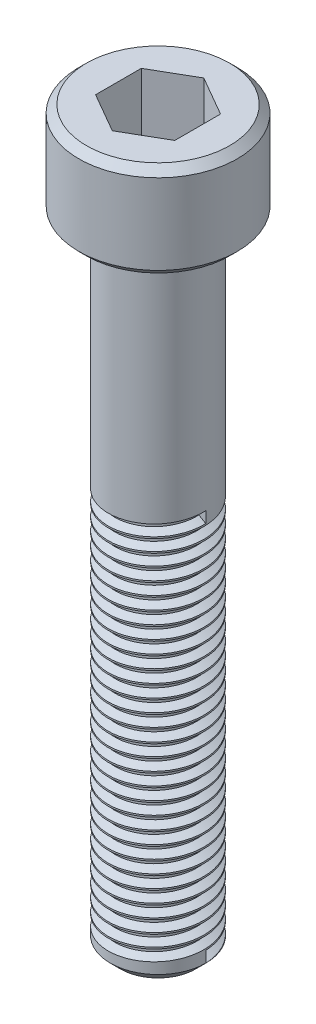
SolidWorks part; units mm, degrees
ref_plane "Front Plane" through (0, 0, 0) normal (0, 0, 1) x (1, 0, 0)
ref_plane "Top Plane" through (0, 0, 0) normal (0, 1, 0) x (1, 0, 0)
ref_plane "Right Plane" through (0, 0, 0) normal (1, 0, 0) x (0, 0, -1)
sketch "Sketch1" plane through (0, 0, 0) normal (0, 0, 1) x (1, 0, 0)
  line L0 (0, 0) -> (0, 43.3309) construction
  line L1 (0, 0) -> (-2.3876, 0)
  line L2 (-2.3876, 0) -> (-2.3876, 31.75)
  line L3 (-2.3876, 31.75) -> (-3.9624, 31.75)
  line L4 (-3.9624, 31.75) -> (-3.9624, 36.5252)
  line L5 (-3.9624, 36.5252) -> (0, 36.5252)
  line L6 (0, 36.5252) -> (0, 0)
  point P8 (-3.9624, 34.1376)
  dimension "D1" = 31.75
  dimension "D2" = 4.7752
  dimension "D3" = 3.9624
  dimension "D4" = 2.3876
revolve "Revolve1" add sketch "Sketch1" angle 360 about L0
chamfer "Chamfer1" distance 0.508 angle 45 1 edges at (0, 0, -2.3876)
chamfer "Chamfer2" distance 0.381 angle 45 2 edges at (0, 36.5252, -3.9624) (0, 31.75, -3.9624)
thread "Thread2" pitch 0.635 method cut profile "Thread Profile2" start angle 0, offset 0, length 19.05, pitch 0.635, diameter 4.7752
ref_plane "Plane2" through (2.3876, 0.508, 0) normal (0, 0, 1) x (1, 0, 0)
sketch "Thread Profile2" plane through (2.3876, 0.508, 0) normal (0, 0, 1) x (1, 0, 0)
  line L0 (0, 0) -> (0, 0.635) construction
  line L11 (0, 0) -> (0, 0.5556)
  line L12 (0, 0.5556) -> (-0.3437, 0.3572)
  line L13 (-0.3437, 0.3572) -> (-0.3437, 0.1984)
  line L15 (-0.3437, 0.1984) -> (0, 0)
  line L17 (-0.3437, 0.2778) -> (0, 0.2778) construction
  point P2 (0, 0)
  dimension "Pitch" = 0.635
  dimension "Profile_Angle" = 60
  dimension "Profile_Land" = 0.1588
  dimension "Profile_Height" = 0.3437
sketch "Sketch10" plane through (0, 36.5252, 0) normal (0, 1, 0) x (1, 0, 0)
  line L1 (-1.9812, 1.1438) -> (-1.9812, -1.1438)
  line L2 (-1.9812, -1.1438) -> (0, -2.2877)
  line L3 (0, -2.2877) -> (1.9812, -1.1438)
  line L4 (1.9812, -1.1438) -> (1.9812, 1.1438)
  line L5 (1.9812, 1.1438) -> (0, 2.2877)
  line L6 (0, 2.2877) -> (-1.9812, 1.1438)
  circle A0 centre (0, 0) radius 1.9812 construction
  point P1 (1.9812, 0)
  dimension "D1" = 3.9624
extrude "Cut-Extrude2" cut sketch "Sketch10" against normal blind 3.302
